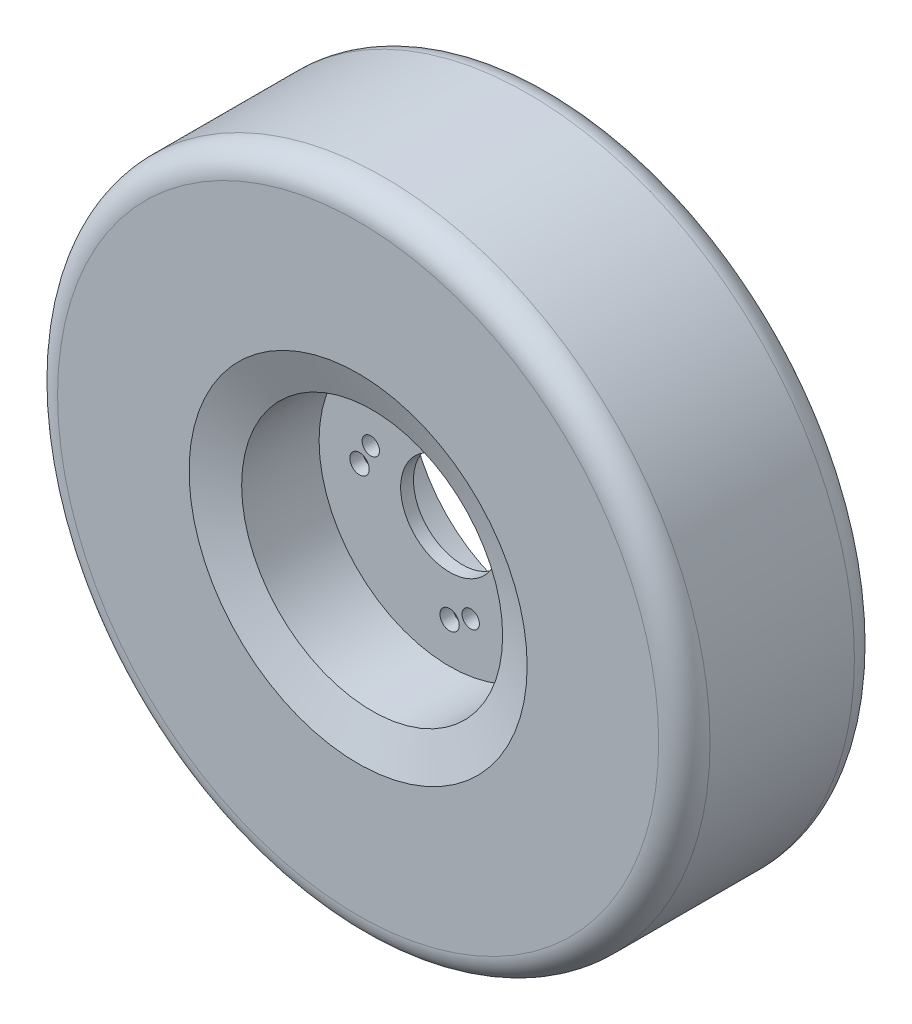
SolidWorks part; units mm, degrees
ref_plane "Front Plane" through (0, 0, 0) normal (0, 0, 1) x (1, 0, 0)
ref_plane "Top Plane" through (0, 0, 0) normal (0, 1, 0) x (1, 0, 0)
ref_plane "Right Plane" through (0, 0, 0) normal (1, 0, 0) x (0, 0, -1)
sketch "Sketch1" plane through (0, 0, 0) normal (0, 0, 1) x (1, 0, 0)
  circle A0 centre (0, 0) radius 50.8
  circle A1 centre (0, 0) radius 127
  dimension "D1" = 254
  dimension "D2" = 101.6
extrude "Boss-Extrude1" add sketch "Sketch1" along normal mid plane 76.2
chamfer "Chamfer1" distance 15 angle 20 2 edges at (50.8, 0, 38.1) (50.8, 0, -38.1) first distance on face at (127, 0, 38.1) first distance on face at (127, 0, -38.1)
fillet "Fillet1" radius 10 2 edges at (127, 0, -38.1) (127, 0, 38.1)
sketch "Sketch2" plane through (0, 0, 0) normal (0, 0, 1) x (1, 0, 0)
  circle A0 centre (0, 0) radius 50.8
  circle A1 centre (0, 0) radius 50.8 construction
  circle A2 centre (0, 0) radius 19.05
  dimension "D1" = 38.1
extrude "Boss-Extrude2" add sketch "Sketch2" along normal mid plane 5
hole_wizard "19/64 (0.29688) Diameter Hole1" positions "Sketch3" profile "Sketch4" hole size "19/64" standard "ANSI Inch"
sketch "Sketch3" plane through (0, 0, 2.5) normal (0, 0, 1) x (1, 0, 0)
  line L0 (0, -35.052) -> (0, 0) construction
  line L1 (0, 0) -> (35.052, 0) construction
  line L3 (0, 35.052) -> (0, 0) construction
  line L4 (0, 0) -> (-35.052, 0) construction
  circle A0 centre (0, 0) radius 35.052 construction
  point P0 (0, 35.052)
  point P2 (35.052, 0)
  point P4 (0, -35.052)
  point P6 (-35.052, 0)
  dimension "D1" = 70.104
sketch "Sketch4" plane through (0, 35.052, 2.5) normal (1, 0, 0) x (0, -1, 0)
  line L0 (0, 0) -> (0, 21.0155)
  line L1 (0, 21.0155) -> (3.7704, 18.75)
  line L2 (3.7704, 18.75) -> (3.7704, 0)
  line L5 (3.7704, 0) -> (0, 0)
  line L10 (0, 21.0155) -> (-3.7704, 18.75) construction
  line L11 (0, -6.35) -> (0, 107.95) construction
  dimension "Hole Dia." = 7.5408
  dimension "Hole Depth" = 18.75
  dimension "Drill Angle" = 118
hole_wizard "1/4 Clearance Hole1" positions "Sketch7" profile "Sketch8" hole size "1/4" standard "ANSI Inch"
sketch "Sketch7" plane through (0, 0, 2.5) normal (0, 0, 1) x (1, 0, 0)
  line L0 (-30.6681, 8.2175) -> (0, 0) construction
  line L1 (0, 0) -> (8.2175, -30.6681) construction
  line L4 (0, 0) -> (22.4506, 22.4506) construction
  line L6 (-35.052, 0) -> (35.052, 0) construction
  line L8 (0, 0) -> (-22.4506, -22.4506) construction
  circle A0 centre (0, 0) radius 31.75 construction
  point P0 (-30.6681, 8.2175)
  point P2 (22.4506, 22.4506)
  point P4 (8.2175, -30.6681)
  dimension "D3" = 63.5
  dimension "D1" = 120
  dimension "D2" = 120
  dimension "D4" = 45
  dimension "D5" = 60
sketch "Sketch8" plane through (-30.6681, 8.2175, 2.5) normal (1, 0, 0) x (0, -1, 0)
  line L0 (0, 0) -> (0, 20.7798)
  line L1 (0, 20.7798) -> (3.3782, 18.75)
  line L2 (3.3782, 18.75) -> (3.3782, 0)
  line L5 (3.3782, 0) -> (0, 0)
  line L10 (0, 20.7798) -> (-3.3782, 18.75) construction
  line L11 (0, -6.35) -> (0, 107.95) construction
  dimension "Hole Dia." = 6.7564
  dimension "Hole Depth" = 18.75
  dimension "Drill Angle" = 118
